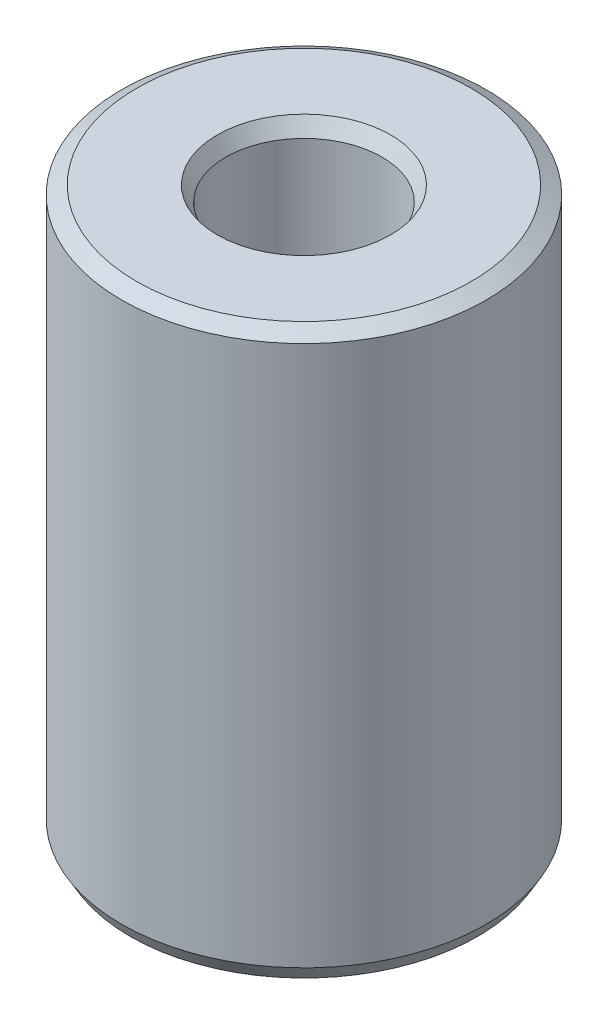
SolidWorks part; units mm, degrees
ref_plane "Front Plane" through (0, 0, 0) normal (0, 0, 1) x (1, 0, 0)
ref_plane "Top Plane" through (0, 0, 0) normal (0, 1, 0) x (1, 0, 0)
ref_plane "Right Plane" through (0, 0, 0) normal (1, 0, 0) x (0, 0, -1)
sketch "Sketch1" plane through (0, 0, 0) normal (0, 1, 0) x (1, 0, 0)
  circle A0 centre (0, 0) radius 27.5
  dimension "SLEEVE_OD" = 55
extrude "Boss-Extrude1" add sketch "Sketch1" along normal blind 85.1134
sketch "Sketch2" plane through (0, 0, 0) normal (0, 1, 0) x (1, 0, 0)
  circle A0 centre (0, 0) radius 11.7784
  dimension "BORE_D" = 23.5569
extrude "Cut-Extrude1" cut sketch "Sketch2" along normal through all
chamfer "Chamfer1" distance 1.2981 angle 60 4 edges at (0, 85.1134, 11.7784) (0, 0, 11.7784) (0, 0, 27.5) (0, 85.1134, 27.5) first distance on face at (0, 85.1134, 11.7784) first distance on face at (0, 0, 11.7784) first distance on face at (0, 85.1134, 27.5)
